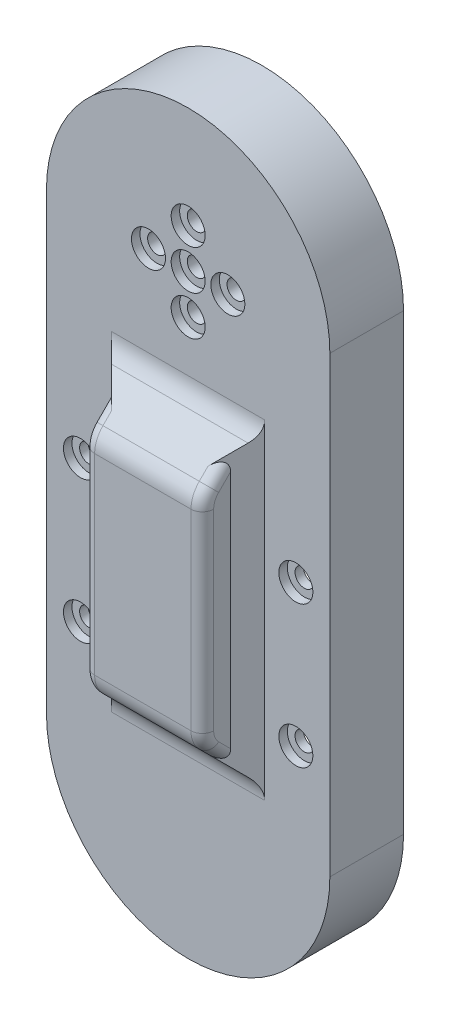
SolidWorks part; units mm, degrees
ref_plane "前视基准面" through (0, 0, 0) normal (0, 0, 1) x (1, 0, 0)
ref_plane "上视基准面" through (0, 0, 0) normal (0, 1, 0) x (1, 0, 0)
ref_plane "右视基准面" through (0, 0, 0) normal (1, 0, 0) x (0, 0, -1)
sketch "草图1" plane through (0, 0, 0) normal (0, 0, 1) x (1, 0, 0)
  line L0 (0, 7) -> (0, 0)
  circle A0 centre (0, 0) radius 15
  circle A1 centre (0, 0) radius 1.65
  circle A2 centre (0, 7) radius 1.65
  circle A3 centre (0, 0) radius 1.65
  circle A4 centre (7, 0) radius 1.65
  circle A5 centre (0, 0) radius 1.65
  circle A6 centre (0, -7) radius 1.65
  circle A7 centre (0, 0) radius 1.65
  circle A8 centre (-7, 0) radius 1.65
  point P19 (0, 0)
  dimension "D3" = 3.3
  dimension "D4" = 30
  dimension "D5" = 3.3
  dimension "D1" = 0
  dimension "D2" = 7
  dimension "D6" = 4
extrude "凸台-拉伸1" add sketch "草图1" along normal blind 8 contours A0 A8 A6 A4 A2 A1 region at (-14.5757, 0, 0)
sketch "草图3" plane through (0, 0, 8) normal (0, 0, 1) x (1, 0, 0)
  line L1 (-25, 0) -> (25, 0)
  line L2 (-25, 0) -> (-25, -80)
  line L3 (-25, -80) -> (25, -80)
  line L4 (25, 0) -> (25, -80)
  circle A0 centre (0, 0) radius 25
  circle A1 centre (0, 0) radius 15 construction
  circle A2 centre (0, 0) radius 15
  circle A3 centre (0, -80) radius 25
  circle M13 centre (0, 0) radius 15
  dimension "D1" = 50
  dimension "D2" = 80
extrude "凸台-拉伸2" add sketch "草图3" against normal blind 3 contours A3 L4 A0 L2 | L1 A0 M13 | L1 A0 M13 | L3 A3 | L3 A3 region at (0, 15.559, 8) region at (20, -0.559, 8) region at (0, -40, 8) region at (0, -90.6103, 8) region at (0, -69.3897, 8)
sketch "草图4" plane through (0, 0, 5) normal (0, 0, -1) x (-1, 0, 0)
  line L2 (25, -80) -> (25, 0)
  line L3 (-25, 0) -> (-25, -80)
  line L4 (25, -80) -> (25, 0)
  line L5 (-25, 0) -> (-25, -80)
  circle A0 centre (0, 0) radius 25
  circle A1 centre (0, 0) radius 22.5
  arc A2 (25, 0) -> (-25, 0) centre (0, 0) ccw
  arc A3 (-25, -80) -> (25, -80) centre (0, -80) ccw
  arc A4 (25, 0) -> (-25, 0) centre (0, 0) ccw
  arc A5 (-25, -80) -> (25, -80) centre (0, -80) ccw
  arc M9 (25, 0) -> (-25, 0) centre (0, 0) ccw
  dimension "D2" = 45
  dimension "D3" = 50
  dimension "D1" = 0
extrude "凸台-拉伸3" add sketch "草图4" along normal blind 10 contours A0 A1 M9 region at (0, -24.2929, 5)
sketch "草图6" plane through (0, 0, 8) normal (0, 0, 1) x (1, 0, 0)
  line L0 (0, 0) -> (0, -80)
  line L2 (-25, 0) -> (-25, -80)
  line L3 (25, -80) -> (25, 0)
  line L4 (-25, 0) -> (-25, -80)
  line L5 (25, -80) -> (25, 0)
  line L6 (-8.5, -60) -> (8.5, -60)
  line L7 (-8.5, -60) -> (-8.5, -30)
  line L8 (-8.5, -30) -> (8.5, -30)
  line L9 (8.5, -60) -> (8.5, -30)
  line L10 (-8.5, -60) -> (8.5, -30) construction
  line L11 (-8.5, -30) -> (8.5, -60) construction
  arc A2 (-25, -80) -> (25, -80) centre (0, -80) ccw
  arc A3 (25, 0) -> (-25, 0) centre (0, 0) ccw
  arc A4 (-25, -80) -> (25, -80) centre (0, -80) ccw
  arc A5 (25, 0) -> (-25, 0) centre (0, 0) ccw
  point P2 (0, -45)
  dimension "D2" = 35
  dimension "D3" = 30
  dimension "D4" = 17
  dimension "D1" = 0
extrude "切除-拉伸1" cut sketch "草图6" against normal blind 4 contours L8 L7 L6 L0 | L6 L9 L8 L0 region at (4.25, -45, 8) region at (-4.25, -45, 8)
fillet "圆角2" radius 1 4 edges at (-8.5, -60, 6.5) (8.5, -60, 6.5) (8.5, -30, 6.5) (-8.5, -30, 6.5)
sketch "草图7" plane through (0, 0, 5) normal (0, 0, -1) x (-1, 0, 0)
  line L0 (0, -80) -> (0, -60) construction
  line L8 (-25, 0) -> (-25, -80)
  line L9 (25, -80) -> (25, 0)
  line L13 (-25, 0) -> (-25, -80)
  line L14 (25, -80) -> (25, 0)
  circle A0 centre (19, -38) radius 1.65
  circle A1 centre (19, -63) radius 1.65
  circle A2 centre (-19, -63) radius 1.65
  circle A3 centre (-19, -38) radius 1.65
  arc A5 (-25, 0) -> (25, 0) centre (0, 0) ccw
  arc A9 (-25, -80) -> (25, -80) centre (0, -80) ccw
  arc A10 (-25, 0) -> (25, 0) centre (0, 0) ccw
  arc A14 (-25, -80) -> (25, -80) centre (0, -80) ccw
  dimension "D4" = 3.3
  dimension "D5" = 3.3
  dimension "D2" = 6
  dimension "D3" = 6
  dimension "D6" = 17
  dimension "D7" = 25
  dimension "D1" = 0
extrude "切除-拉伸2" cut sketch "草图7" against normal blind 3.3 contours A1 | A0 | A3 | A2 region at (-19, -38, 5) region at (-19, -63, 5)
sketch "草图8" plane through (0, 0, 5) normal (0, 0, -1) x (-1, 0, 0)
  line L0 (23, -80) -> (23, -9.798)
  line L1 (25, -80) -> (23, -80)
  line L2 (-23, -80) -> (-23, -9.798)
  line L8 (-25, 0) -> (-25, -80)
  line L9 (25, -80) -> (25, 0)
  line L13 (-25, 0) -> (-25, -80)
  line L14 (25, -80) -> (25, 0)
  circle A0 centre (0, -80) radius 23
  arc A5 (-25, 0) -> (25, 0) centre (0, 0) ccw
  arc A9 (-25, -80) -> (25, -80) centre (0, -80) ccw
  arc A10 (-25, 0) -> (25, 0) centre (0, 0) ccw
  arc A14 (-25, -80) -> (25, -80) centre (0, -80) ccw
  arc M15 (25, 0) -> (-25, 0) centre (0, 0) cw
  arc M21 (25, 0) -> (-25, 0) centre (0, 0) cw
  line M22 (-25, 0) -> (-25, -80)
  arc M23 (-25, -80) -> (25, -80) centre (0, -80) ccw
  line M24 (25, -80) -> (25, 0)
  dimension "D2" = 360
  dimension "D3" = 2
  dimension "D1" = 0
extrude "凸台-拉伸5" add sketch "草图8" along normal blind 10 contours A0 L2 L1 M21 M22 M23 | L1 L0 M24 M15 region at (-24.0177, -43.257, 5) region at (-24, -81.163, 5)
sketch "草图9" plane through (0, 0, 8) normal (0, 0, 1) x (1, 0, 0)
  line L0 (-8.5, -59) -> (-8.5, -31) construction
  line L1 (-8.5, -59) -> (-8.5, -31)
  line L2 (-25, 0) -> (-25, -80)
  line L3 (25, -80) -> (25, 0)
  line L4 (-25, 0) -> (-25, -80)
  line L5 (25, -80) -> (25, 0)
  line L6 (-7.5, -60) -> (7.5, -60) construction
  line L7 (-7.5, -30) -> (7.5, -30) construction
  line L8 (8.5, -59) -> (8.5, -31) construction
  line L9 (-7.5, -60) -> (7.5, -60)
  line L10 (-7.5, -30) -> (7.5, -30)
  line L11 (8.5, -59) -> (8.5, -31)
  line L12 (0, -30) -> (0, -60) construction
  line L14 (-10.5, -28) -> (10.5, -28)
  line L15 (-10.5, -28) -> (-10.5, -62)
  line L16 (-10.5, -62) -> (10.5, -62)
  line L17 (10.5, -28) -> (10.5, -62)
  arc A0 (7.5, -60) -> (8.5, -59) centre (7.5, -59) ccw construction
  arc A1 (-8.5, -59) -> (-7.5, -60) centre (-7.5, -59) ccw construction
  arc A2 (-25, -80) -> (25, -80) centre (0, -80) ccw
  arc A3 (25, 0) -> (-25, 0) centre (0, 0) ccw
  arc A4 (-25, -80) -> (25, -80) centre (0, -80) ccw
  arc A5 (25, 0) -> (-25, 0) centre (0, 0) ccw
  arc A6 (8.5, -31) -> (7.5, -30) centre (7.5, -31) ccw construction
  arc A7 (-7.5, -30) -> (-8.5, -31) centre (-7.5, -31) ccw construction
  arc A8 (7.5, -60) -> (8.5, -59) centre (7.5, -59) ccw
  arc A9 (-8.5, -59) -> (-7.5, -60) centre (-7.5, -59) ccw
  arc A10 (8.5, -31) -> (7.5, -30) centre (7.5, -31) ccw
  arc A11 (-7.5, -30) -> (-8.5, -31) centre (-7.5, -31) ccw
  line M30 (7.5, -60) -> (-7.5, -60)
  arc M31 (-7.5, -60) -> (-8.5, -59) centre (-7.5, -59) cw
  line M32 (-8.5, -59) -> (-8.5, -31)
  arc M33 (-8.5, -31) -> (-7.5, -30) centre (-7.5, -31) cw
  line M34 (-7.5, -30) -> (7.5, -30)
  arc M35 (7.5, -30) -> (8.5, -31) centre (7.5, -31) cw
  line M36 (8.5, -31) -> (8.5, -59)
  arc M37 (8.5, -59) -> (7.5, -60) centre (7.5, -59) cw
  dimension "D2" = 2
  dimension "D3" = 2
  dimension "D4" = 2
  dimension "D5" = 2
  dimension "D1" = 0
extrude "凸台-拉伸6" add sketch "草图9" along normal blind 8 contours L17 L14 L15 L16 L9 L10 M37 M30 M31 M32 M33 M34 M35 M36 region at (0, -28.3996, 8)
chamfer "倒角1" distance 10 angle 45 1 edges at (0, -62, 8)
chamfer "倒角2" distance 10 angle 45 1 edges at (0, -28, 8)
sketch "草图10" plane through (0, 0, 16) normal (0, 0, 1) x (1, 0, 0)
  line L4 (10.5, -64) -> (10.5, -26)
  line L5 (10.5, -26) -> (-10.5, -26)
  line L6 (-10.5, -26) -> (-10.5, -64)
  line L7 (-10.5, -64) -> (10.5, -64)
  line L8 (10.5, -64) -> (10.5, -26)
  line L9 (10.5, -26) -> (-10.5, -26)
  line L10 (-10.5, -26) -> (-10.5, -64)
  line L11 (-10.5, -64) -> (10.5, -64)
  dimension "D1" = 0
extrude "凸台-拉伸7" add sketch "草图10" against normal blind 1.5
fillet "圆角3" radius 5 4 edges at (0, -26, 16) (0, -64, 16) (0, -72, 8) (0, -18, 8)
chamfer "倒角4" distance 5 angle 45 8 edges at (0, -60, 5) (-8.2071, -59.7071, 5) (8.2071, -59.7071, 5) (-8.5, -45, 5) (8.5, -45, 5) (-8.2071, -30.2929, 5) (8.2071, -30.2929, 5) (0, -30, 5)
chamfer "倒角6" distance 3 angle 45 2 edges at (10.5, -45, 8) (-10.5, -45, 8)
sketch "草图12" plane through (0, 0, 8) normal (0, 0, 1) x (1, 0, 0)
  circle A0 centre (19, -63) radius 1.65 construction
  circle A1 centre (19, -38) radius 1.65 construction
  circle A2 centre (-19, -63) radius 1.65 construction
  circle A3 centre (-19, -38) radius 1.65 construction
  circle A4 centre (0, -7) radius 1.65 construction
  circle A5 centre (7, 0) radius 1.65 construction
  circle A6 centre (0, 0) radius 1.65 construction
  circle A7 centre (0, 7) radius 1.65 construction
  circle A8 centre (-7, 0) radius 1.65 construction
  circle A9 centre (19, -63) radius 1.65
  circle A10 centre (19, -38) radius 1.65
  circle A11 centre (-19, -63) radius 1.65
  circle A12 centre (-19, -38) radius 1.65
  circle A13 centre (0, -7) radius 1.65
  circle A14 centre (7, 0) radius 1.65
  circle A15 centre (0, 0) radius 1.65
  circle A16 centre (0, 7) radius 1.65
  circle A17 centre (-7, 0) radius 1.65
  circle A18 centre (-19, -38) radius 3
  circle A19 centre (-19, -63) radius 3
  circle A20 centre (19, -38) radius 1.65
  circle A21 centre (19, -63) radius 3
  circle A22 centre (7, 0) radius 3
  circle A23 centre (0, 7) radius 3
  circle A24 centre (0, 0) radius 3
  circle A25 centre (-7, 0) radius 3
  circle A26 centre (0, -7) radius 3
  circle A27 centre (19, -38) radius 3
  circle M8 centre (19, -38) radius 1.65
  circle M9 centre (-19, -38) radius 1.65
  circle M11 centre (0, 0) radius 1.65
  circle M12 centre (-7, 0) radius 1.65
  circle M13 centre (0, -7) radius 1.65
  circle M14 centre (7, 0) radius 1.65
  circle M15 centre (0, 7) radius 1.65
  circle M20 centre (19, -63) radius 1.65
  dimension "D1" = 6
  dimension "D2" = 6
  dimension "D3" = 6
  dimension "D4" = 6
  dimension "D5" = 6
  dimension "D6" = 6
  dimension "D7" = 6
  dimension "D8" = 6
  dimension "D9" = 6
extrude "切除-拉伸3" cut sketch "草图12" against normal blind 1.5 contours A23 M15 | A25 M12 | A24 M11 | A22 M14 | A26 M13 | A18 M9 | A21 M20 | A27 M8 | A19 | A10 region at (-21.9151, -38, 8) region at (16.0849, -63, 8) region at (4.0849, 0, 8) region at (-2.9151, 7, 8) region at (-2.9151, 0, 8) region at (-9.9151, 0, 8) region at (-2.9151, -7, 8) region at (16.0849, -38, 8)
fillet "圆角4" radius 2 10 edges at (10.5, -22.7678, 12.7678) (10.5, -26.1577, 15.6194) (10.5, -67.2322, 12.7678) (10.5, -63.8423, 15.6194) (-10.5, -22.7678, 12.7678) (-10.5, -26.1577, 15.6194) (-10.5, -67.2322, 12.7678) (-10.5, -63.8423, 15.6194) (10.5, -45, 16) (-10.5, -45, 16)
